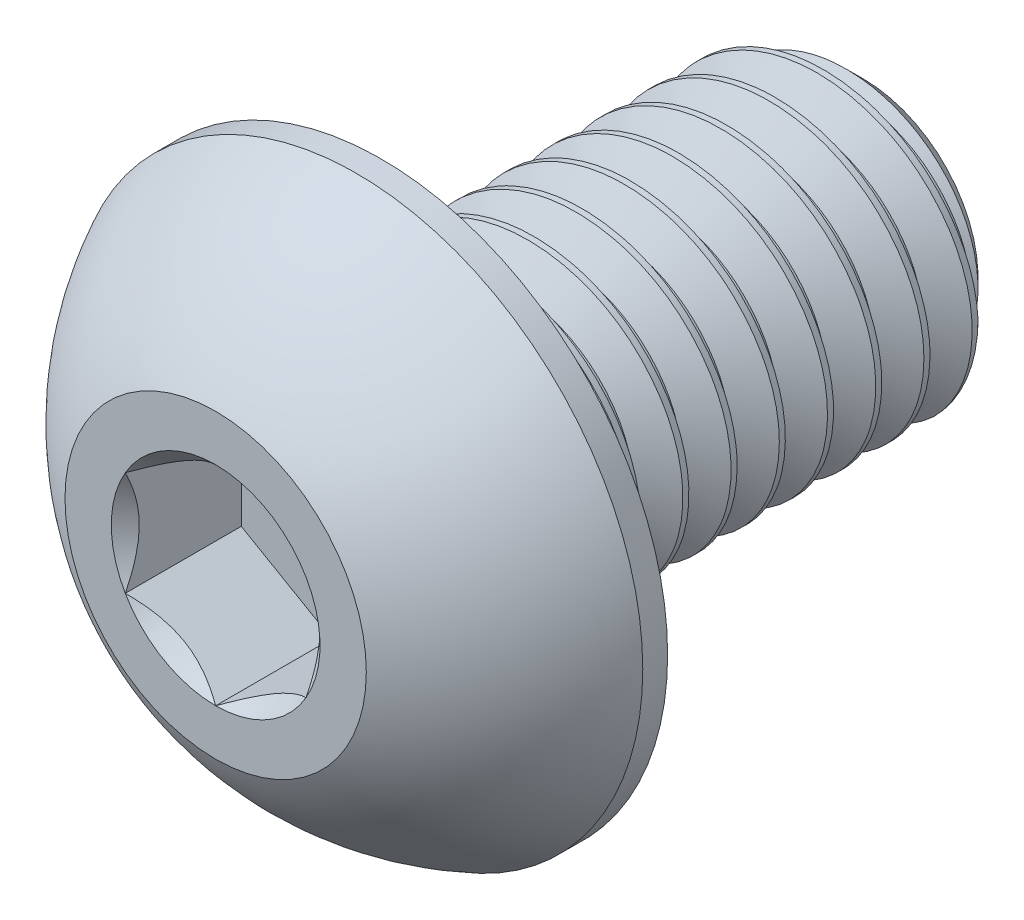
SolidWorks part; units mm, degrees
ref_plane "Front" through (0, 0, 0) normal (0, 0, 1) x (1, 0, 0)
ref_plane "Top" through (0, 0, 0) normal (0, 1, 0) x (1, 0, 0)
ref_plane "Right" through (0, 0, 0) normal (1, 0, 0) x (0, 0, -1)
sketch "Sketch1" plane through (0, 0, 0) normal (1, 0, 0) x (0, 0, -1)
  line L2 (2.75, 2.5) -> (10.75, 2.5)
  line L3 (10.75, 2.5) -> (10.75, 0)
  line L4 (10.75, 0) -> (2.75, 0)
  line L6 (2.3375, 4.75) -> (2.75, 4.75) construction
  line L7 (10.75, 2.5) -> (10.75, -2.5) construction
  line L8 (0, 0) -> (2.75, 0) construction
  line L9 (2.75, 4.75) -> (2.75, -4.75) construction
  line L11 (2.75, 2.5) -> (2.75, 0)
  line L13 (0, 1.5) -> (0, -1.5) construction
  line L14 (0, 1.5) -> (0, 2.5) construction
  arc A3 (0, 2.5) -> (2.3375, 4.75) centre (4.6581, 0) cw construction
  dimension "D1" = 0.4125
  dimension "Head Ht" = 2.75
  dimension "Head Dia" = 9.5
  dimension "Dia" = 5
  dimension "Lg" = 8
  dimension "Hex" = 3
revolve "Revolve1" add sketch "Sketch1" angle 360 mid plane about L4
sketch "Sketch3" plane through (0, 0, -10.75) normal (0, 0, -1) x (-1, 0, 0)
  circle A0 centre (0, 0) radius 2.5
curve "Helix/Spiral1" pitch 0.8 height 8.8 radius 2.5 centre (0, 0, -10.75) axis (0, 0, 1) start towards (0, 1, 0)
sketch "Sketch2" plane through (0, 0, 0) normal (1, 0, 0) x (0, 0, -1)
  line L0 (10.75, 2.5) -> (11.45, 2.5)
  line L1 (11.45, 2.5) -> (11.15, 1.9804)
  line L2 (11.15, 1.9804) -> (11.05, 1.9804)
  line L3 (11.05, 1.9804) -> (10.75, 2.5)
  line L4 (10.9, 2.2402) -> (11.3, 2.2402) construction
  dimension "D1" = 60
  dimension "D2" = 0.1
  dimension "D3" = 0.4
chamfer "Chamfer1" distance 0.6 angle 45 1 edges at (0, 2.5, -10.75)
sweep "Cut-Sweep1" cut profiles "Sketch2" path "Helix/Spiral1"
sketch "Sketch7" plane through (0, 0, 0) normal (1, 0, 0) x (0, 0, -1)
  line L6 (2.3375, 4.75) -> (2.75, 4.75) construction
  line L8 (0, 0) -> (2.75, 0) construction
  line L11 (2.75, 4.75) -> (2.75, -4.75) construction
  line L12 (2.3375, 4.75) -> (2.75, 4.75)
  line L13 (0, 0) -> (2.75, 0)
  line L14 (0, 1.5) -> (0, -1.5) construction
  line L15 (2.75, 4.75) -> (2.75, 0)
  line L16 (0, 2.5) -> (0, 0)
  arc A2 (2.3375, 4.75) -> (0, 2.5) centre (4.6581, 0) ccw construction
  arc A3 (2.3375, 4.75) -> (0, 2.5) centre (4.6581, 0) ccw
revolve "Revolve2" add sketch "Sketch7" angle 360 mid plane about L13
sketch "Sketch5" plane through (0, 0, 0) normal (0, 0, 1) x (1, 0, 0)
  line L1 (1.5, -0.866) -> (1.5, 0.866)
  line L2 (1.5, 0.866) -> (0, 1.7321)
  line L3 (0, 1.7321) -> (-1.5, 0.866)
  line L4 (-1.5, 0.866) -> (-1.5, -0.866)
  line L5 (-1.5, -0.866) -> (0, -1.7321)
  line L6 (0, -1.7321) -> (1.5, -0.866)
  circle A0 centre (0, 0) radius 1.5 construction
extrude "Cut-Extrude2" cut sketch "Sketch5" against normal blind 1.925
sketch "Sketch6" plane through (0, 0, 0) normal (0, 0, 1) x (1, 0, 0)
  circle A0 centre (0, 0) radius 1.7321
extrude "Cut-Extrude3" cut sketch "Sketch6" against normal blind 1.925 draft 45
sketch "Sketch9" [suppressed] plane through (0, 0, -6.6) normal (0, 0, 1) x (1, 0, 0)
  circle A2 centre (0, 0) radius 6
extrude "Boss-Extrude2" [suppressed] add sketch "Sketch9" against normal offset from surface (19 mm away) 32
sketch "Sketch10" plane through (0, 0, 0) normal (1, 0, 0) x (0, 0, -1)
  line L0 (10.75, 2.5) -> (10.75, -2.5) construction
  point P0 (9.55, -2.5)
  dimension "D1" = 1.2
equation "\"D3@Helix/Spiral1\" = \"Lg@Sketch1\" + \"D4@Helix/Spiral1\""
equation "\"D2@Sketch2\" = \"D4@Helix/Spiral1\" * .125"
equation "\"D3@Sketch2\" = \"D4@Helix/Spiral1\" * .5"
equation "\"D1@Chamfer1\" = \"D4@Helix/Spiral1\" * .75"
equation "\"D1@Cut-Extrude2\" = \"Head Ht@Sketch1\" * .7"
equation "\"D1@Sketch1\" = \"Head Ht@Sketch1\" * .15"
equation "\"D1@Sketch10\" = \"D4@Helix/Spiral1\" * 1.5"
equation "\"D1@Cut-Extrude3\" = \"D1@Cut-Extrude2\""
